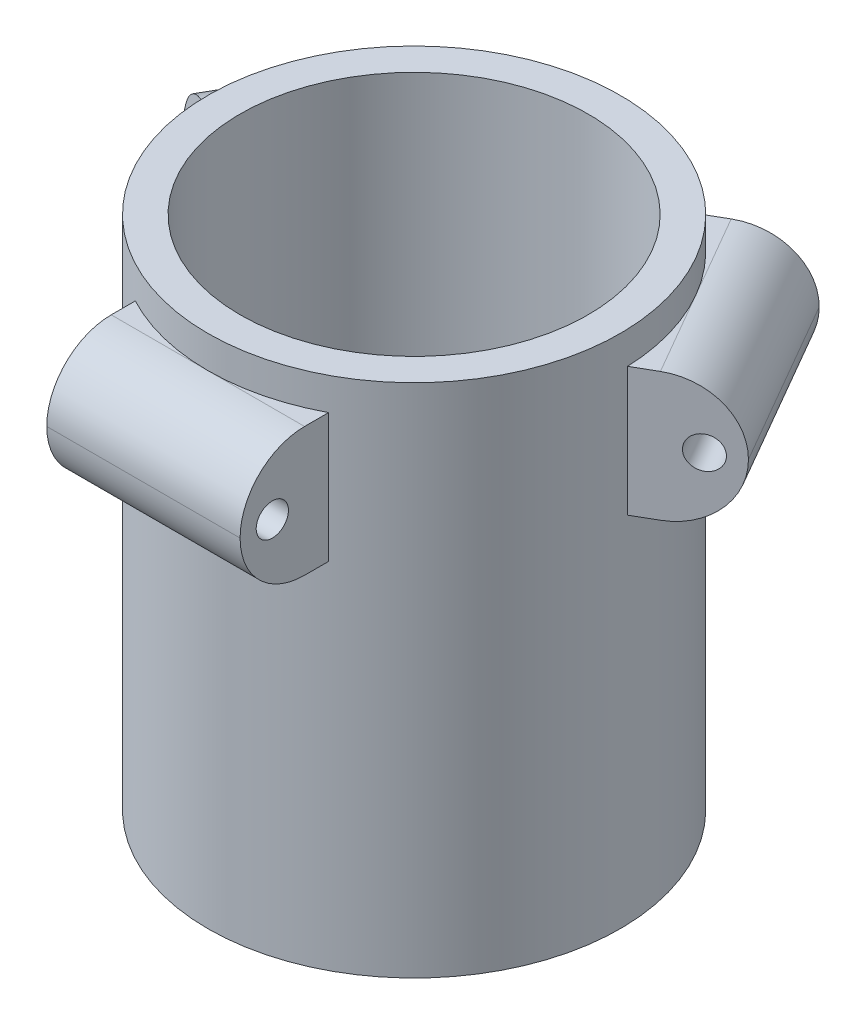
SolidWorks part; units mm, degrees
ref_plane "Front Plane" through (0, 0, 0) normal (0, 0, 1) x (1, 0, 0)
ref_plane "Top Plane" through (0, 0, 0) normal (0, 1, 0) x (1, 0, 0)
ref_plane "Right Plane" through (0, 0, 0) normal (1, 0, 0) x (0, 0, -1)
sketch "Sketch1" plane through (0, 0, 0) normal (0, 1, 0) x (1, 0, 0)
  circle A0 centre (0, 0) radius 20.32
  dimension "D1" = 40.64
extrude "Boss-Extrude1" add sketch "Sketch1" along normal blind 50.8
shell "Shell1" thickness 3.175 removed face at (0, 50.8, 20.32)
sketch "Sketch2" plane through (0, 3.175, 0) normal (0, 1, 0) x (1, 0, 0)
  circle A0 centre (0, 0) radius 4.064
  dimension "D1" = 8.128
extrude "Cut-Extrude1" cut sketch "Sketch2" along normal through all and the other way blind 46.482
sketch "Sketch3" plane through (0, 0, 0) normal (0, -1, 0) x (1, 0, 0)
  line L0 (0, -20.32) -> (0, 20.32) construction
  line L1 (-20.32, 0) -> (20.32, 0) construction
  line L2 (0, 20.32) -> (-17.5976, -10.16) construction
  line L3 (-17.5976, -10.16) -> (17.5976, -10.16) construction
  line L4 (17.5976, -10.16) -> (0, 20.32) construction
  line L7 (9.525, 17.9493) -> (9.525, 26.67)
  line L8 (9.525, 26.67) -> (-9.525, 26.67)
  line L9 (-9.525, 17.9493) -> (-9.525, 26.67)
  line L10 (0, 20.32) -> (-9.525, 26.67) construction
  line L11 (9.525, 26.67) -> (0, 20.32) construction
  circle A1 centre (0, 0) radius 20.32
  circle A2 centre (0, 0) radius 20.32
  point P6 (0, 0)
  point P9 (0, 0)
  circle M7 centre (0, 0) radius 20.32
  dimension "D2" = 19.05
  dimension "D3" = 6.35
  dimension "D4" = 8.7207
  dimension "D1" = 0
extrude "Boss-Extrude2" add sketch "Sketch3" against normal blind 12.7 from offset 34.925 contours L9 L7 L8 M7 region at (0, 0, 23.0752) offset against normal yes
sketch "Sketch4" plane through (9.525, 0, 0) normal (1, 0, 0) x (0, 0, -1)
  line L0 (-26.67, 41.275) -> (-23.495, 41.275) construction
  line L4 (-26.67, 34.925) -> (-17.9493, 34.925)
  line L5 (-17.9493, 34.925) -> (-17.9493, 47.625)
  line L6 (-17.9493, 47.625) -> (-26.67, 47.625)
  line L7 (-26.67, 47.625) -> (-26.67, 34.925)
  line L8 (-26.67, 34.925) -> (-17.9493, 34.925)
  line L9 (-17.9493, 34.925) -> (-17.9493, 47.625)
  line L10 (-17.9493, 47.625) -> (-26.67, 47.625)
  line L11 (-26.67, 47.625) -> (-26.67, 34.925)
  circle A0 centre (-23.495, 41.275) radius 1.5875
  dimension "D2" = 3.175
  dimension "D3" = 3.175
  dimension "D1" = 0
extrude "Cut-Extrude2" cut sketch "Sketch4" against normal up to surface (19.05 mm away) contours A0 up to face at (-9.525, 41.275, 22.3096)
fillet "Fillet1" radius 6.35 2 edges at (0, 47.625, 26.67) (0, 34.925, 26.67)
pattern_circular "CirPattern1" count 3 over 360 about axis through (0, -43.307, 0) along (0, 1, 0) of "Boss-Extrude2", "Cut-Extrude2", "Fillet1"
